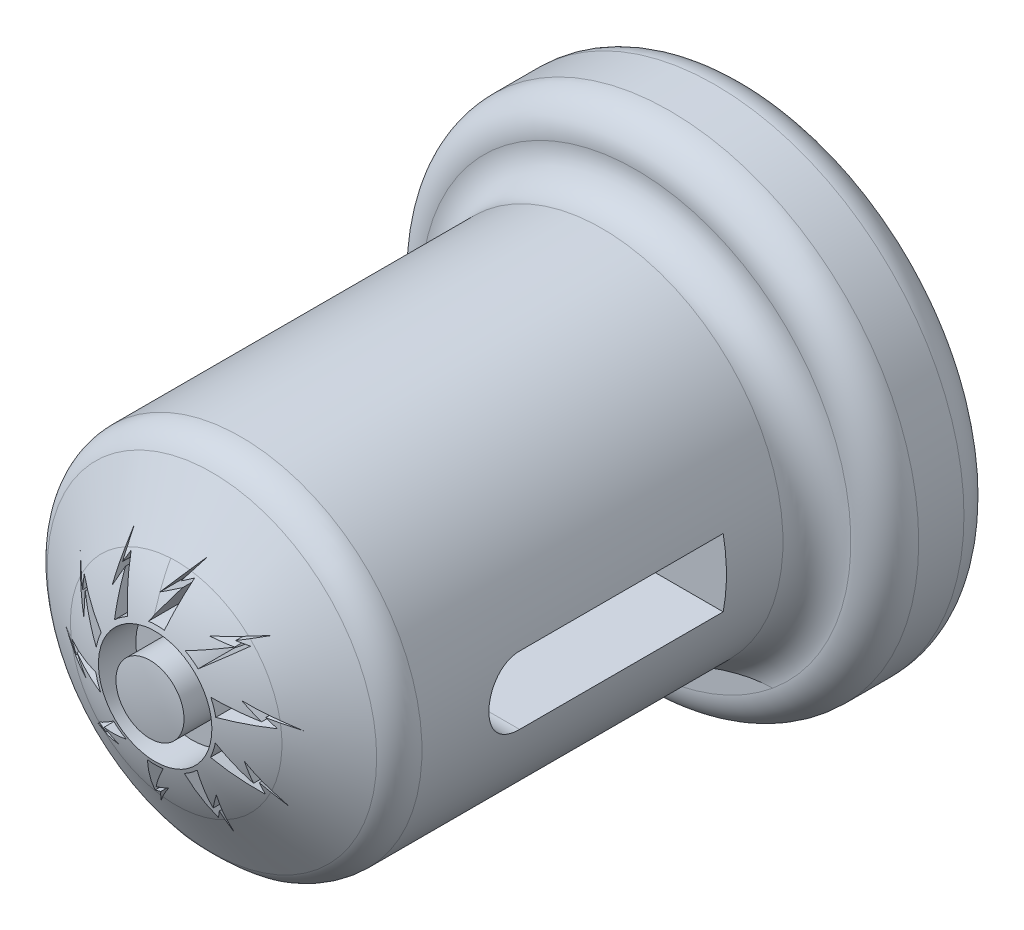
SolidWorks part; units mm, degrees
ref_plane "Alzado" through (0, 0, 0) normal (0, 0, 1) x (1, 0, 0)
ref_plane "Planta" through (0, 0, 0) normal (0, 1, 0) x (1, 0, 0)
ref_plane "Vista lateral" through (0, 0, 0) normal (1, 0, 0) x (0, 0, -1)
sketch "Croquis1" plane through (0, 0, 0) normal (0, 0, 1) x (1, 0, 0)
  line L0 (3.2046, -7.3301) -> (-3.2046, -7.3301)
  line L1 (2.5, -4.3301) -> (-2.5, -4.3301)
  arc A0 (2.5, -4.3301) -> (-2.5, -4.3301) centre (0, 0) ccw
  arc A1 (3.2046, -7.3301) -> (-3.2046, -7.3301) centre (0, 0) ccw
  point P1 (4.6507, -1.8359)
  point P6 (0, 0)
  point P7 (0, -4.3301)
  dimension "D1" = 10
  dimension "D2" = 5
  dimension "D3" = 3
extrude "Saliente-Extruir1" add sketch "Croquis1" along normal blind 23.3
sketch "Croquis2" plane through (0, 0, 0) normal (0, 0, -1) x (-1, 0, 0)
  line L0 (2.5, -4.3301) -> (-2.5, -4.3301) construction
  line L1 (2.5, -4.3301) -> (-2.5, -4.3301)
  circle A0 centre (0, 0) radius 11
  arc A1 (2.5, -4.3301) -> (-2.5, -4.3301) centre (0, 0) ccw construction
  arc A2 (2.5, -4.3301) -> (-2.5, -4.3301) centre (0, 0) ccw
  dimension "D1" = 22
extrude "Saliente-Extruir2" add sketch "Croquis2" against normal blind 5
sketch "Croquis3" plane through (0, 0, 0) normal (1, 0, 0) x (0, 0, -1)
  line L0 (-23.3, 0) -> (-23.3, 8)
  line L2 (-23.3, 8) -> (-25.3212, 4.6757)
  line L3 (-26.6311, 0) -> (-23.3, 0)
  arc A0 (-25.3212, 4.6757) -> (-26.6311, 0) centre (-17.6311, 0) ccw
  point P2 (0, 0)
  point P8 (0, 0)
  dimension "D2" = 9
  dimension "D1" = 31.3
revolve "Revolución1" add sketch "Croquis3" angle 360 about L3
sketch "Croquis4" plane through (0, 0, 23.3) normal (0, 0, -1) x (-1, 0, 0)
  line L1 (3.2046, -7.3301) -> (-3.2046, -7.3301)
  line L2 (3.2046, -7.3301) -> (-3.2046, -7.3301)
  arc A1 (-3.2046, -7.3301) -> (3.2046, -7.3301) centre (0, 0) ccw
  arc A2 (-3.2046, -7.3301) -> (3.2046, -7.3301) centre (0, 0) ccw
  dimension "D1" = 0
extrude "Cortar-Extruir1" cut sketch "Croquis4" against normal up to next
fillet "Redondeo1" radius 1.5 4 edges at (-11, 0, 0) (-11, 0, 5) (0, 8, 5) (0, 8, 23.3)
fillet "Redondeo2" radius 1 2 edges at (0, -4.3301, 0) (0, 5, 0)
ref_plane "Plano1" through (0, 0, 26.6311) normal (0, 0, 1) x (1, 0, 0)
sketch "Croquis5" plane through (0, 0, 26.6311) normal (0, 0, 1) x (1, 0, 0)
  line L0 (1.3026, 2.3441) -> (2.8816, 2.9738)
  line L1 (-0.324, 2.662) -> (0.5833, 4.0996)
  line L2 (0.5833, 4.0996) -> (-0.19, 3.662)
  line L3 (-0.19, 3.662) -> (1.0396, 5.192)
  line L4 (1.0396, 5.192) -> (0.4463, 4.2519)
  line L5 (0.4463, 4.2519) -> (0.876, 4.4951)
  line L6 (0.876, 4.4951) -> (0.376, 2.662)
  line L7 (2.8816, 2.9738) -> (1.9987, 3.0743)
  line L8 (1.9987, 3.0743) -> (3.8929, 3.5894)
  line L9 (3.8929, 3.5894) -> (2.8603, 3.1775)
  line L10 (2.8603, 3.1775) -> (3.3508, 3.1217)
  line L11 (3.3508, 3.1217) -> (1.8689, 1.9326)
  line L12 (2.4316, 1.1308) -> (4.0792, 0.7121)
  line L13 (4.0792, 0.7121) -> (3.4241, 1.3124)
  line L14 (3.4241, 1.3124) -> (5.2592, 0.6157)
  line L15 (5.2592, 0.6157) -> (4.1817, 0.8895)
  line L16 (4.1817, 0.8895) -> (4.5457, 0.5559)
  line L17 (4.5457, 0.5559) -> (2.6479, 0.465)
  line L18 (2.6319, -0.5144) -> (3.7187, -1.8216)
  line L19 (3.7187, -1.8216) -> (3.5415, -0.9509)
  line L20 (3.5415, -0.9509) -> (4.6166, -2.5932)
  line L21 (4.6166, -2.5932) -> (3.9059, -1.7384)
  line L22 (3.9059, -1.7384) -> (4.0044, -2.2222)
  line L23 (4.0044, -2.2222) -> (2.4155, -1.1802)
  line L24 (1.8268, -1.9632) -> (1.9378, -3.6595)
  line L25 (1.9378, -3.6595) -> (2.3062, -2.8509)
  line L26 (2.3062, -2.8509) -> (2.2107, -4.8115)
  line L27 (2.2107, -4.8115) -> (2.1381, -3.7022)
  line L28 (2.1381, -3.7022) -> (1.9334, -4.1515)
  line L29 (1.9334, -4.1515) -> (1.2605, -2.3746)
  line L30 (0.324, -2.662) -> (-0.5833, -4.0996)
  line L31 (-0.5833, -4.0996) -> (0.19, -3.662)
  line L32 (0.19, -3.662) -> (-1.0396, -5.192)
  line L33 (-1.0396, -5.192) -> (-0.4463, -4.2519)
  line L34 (-0.4463, -4.2519) -> (-0.876, -4.4951)
  line L35 (-0.876, -4.4951) -> (-0.376, -2.662)
  line L36 (-1.3026, -2.3441) -> (-2.8816, -2.9738)
  line L37 (-2.8816, -2.9738) -> (-1.9987, -3.0743)
  line L38 (-1.9987, -3.0743) -> (-3.8929, -3.5894)
  line L39 (-3.8929, -3.5894) -> (-2.8603, -3.1775)
  line L40 (-2.8603, -3.1775) -> (-3.3508, -3.1217)
  line L41 (-3.3508, -3.1217) -> (-1.8689, -1.9326)
  line L42 (-2.4316, -1.1308) -> (-4.0792, -0.7121)
  line L43 (-4.0792, -0.7121) -> (-3.4241, -1.3124)
  line L44 (-3.4241, -1.3124) -> (-5.2592, -0.6157)
  line L45 (-5.2592, -0.6157) -> (-4.1817, -0.8895)
  line L46 (-4.1817, -0.8895) -> (-4.5457, -0.5559)
  line L47 (-4.5457, -0.5559) -> (-2.6479, -0.465)
  line L48 (-2.6319, 0.5144) -> (-3.7187, 1.8216)
  line L49 (-3.7187, 1.8216) -> (-3.5415, 0.9509)
  line L50 (-3.5415, 0.9509) -> (-4.6166, 2.5932)
  line L51 (-4.6166, 2.5932) -> (-3.9059, 1.7384)
  line L52 (-3.9059, 1.7384) -> (-4.0044, 2.2222)
  line L53 (-4.0044, 2.2222) -> (-2.4155, 1.1802)
  line L54 (-1.8268, 1.9632) -> (-1.9378, 3.6595)
  line L55 (-1.9378, 3.6595) -> (-2.3062, 2.8509)
  line L56 (-2.3062, 2.8509) -> (-2.2107, 4.8115)
  line L57 (-2.2107, 4.8115) -> (-2.1381, 3.7022)
  line L58 (-2.1381, 3.7022) -> (-1.9334, 4.1515)
  line L59 (-1.9334, 4.1515) -> (-1.2605, 2.3746)
  circle A0 centre (0.026, -0.0152) radius 1.5
  circle A1 centre (0.026, -0.0152) radius 2.5
  arc A2 (0.376, 2.662) -> (-0.324, 2.662) centre (0.026, -0.0152) ccw
  arc A3 (1.8689, 1.9326) -> (1.3026, 2.3441) centre (0.0121, -0.0276) ccw
  arc A4 (2.6479, 0.465) -> (2.4316, 1.1308) centre (-0.0064, -0.0294) ccw
  arc A5 (2.4155, -1.1802) -> (2.6319, -0.5144) centre (-0.0225, -0.02) ccw
  arc A6 (1.2605, -2.3746) -> (1.8268, -1.9632) centre (-0.03, -0.003) ccw
  arc A7 (-0.376, -2.662) -> (0.324, -2.662) centre (-0.026, 0.0152) ccw
  arc A8 (-1.8689, -1.9326) -> (-1.3026, -2.3441) centre (-0.0121, 0.0276) ccw
  arc A9 (-2.6479, -0.465) -> (-2.4316, -1.1308) centre (0.0064, 0.0294) ccw
  arc A10 (-2.4155, 1.1802) -> (-2.6319, 0.5144) centre (0.0225, 0.02) ccw
  arc A11 (-1.2605, 2.3746) -> (-1.8268, 1.9632) centre (0.03, 0.003) ccw
  point P1 (0.026, 2.6848)
  point P4 (0.026, -0.0152)
  point P11 (0.026, -0.0152)
  point P38 (0.026, -0.0152)
  point P91 (0, 0)
  dimension "D1" = 3
  dimension "D12" = 2.7
  dimension "D9" = 5
  dimension "D2" = 0.2
  dimension "D3" = 1.9
  dimension "D4" = 1.7
  dimension "D5" = 0.7
  dimension "D6" = 0.5
  dimension "D7" = 1
  dimension "D8" = 2.53
  dimension "D10" = 0.566
  dimension "D11" = 0.6637
  dimension "D13" = 0.026
  dimension "D14" = 10
  dimension "D15" = 0.0064
extrude "Cortar-Extruir2" cut sketch "Croquis5" against normal blind 2
chamfer "Chaflán1" distance 0.5 angle 45 1 edges at (0, 5, 23.3)
ref_plane "Plano2" through (8, 0, 0) normal (1, 0, 0) x (0, 0, -1)
sketch "Croquis6" plane through (8, 0, 0) normal (1, 0, 0) x (0, 0, -1)
  line L0 (-18, 0) -> (-5, 0) construction
  line L1 (-18, 1.5) -> (-5, 1.5) construction
  line L2 (-18, -1.5) -> (-5, -1.5) construction
  line L3 (-23.3, -4.3301) -> (-23.3, 4.5) construction
  line L4 (-9, -1.5) -> (-9, 1.5)
  line L5 (-9, 1.5) -> (-18, 1.5)
  line L6 (-18, -1.5) -> (-9, -1.5)
  line L7 (-5, -7.3301) -> (-5, 9.5) construction
  arc A0 (-18, 1.5) -> (-18, -1.5) centre (-18, 0) ccw construction
  arc A1 (-5, -1.5) -> (-5, 1.5) centre (-5, 0) ccw construction
  arc A2 (-18, 1.5) -> (-18, -1.5) centre (-18, 0) ccw
  point P3 (-11.5, 0)
  point P8 (-19.5, 0)
  point P11 (-3.5, 0)
  dimension "D1" = 3
  dimension "D2" = 3.8
  dimension "D3" = 16
  dimension "D4" = 4
extrude "Cortar-Extruir3" cut sketch "Croquis6" against normal up to next
